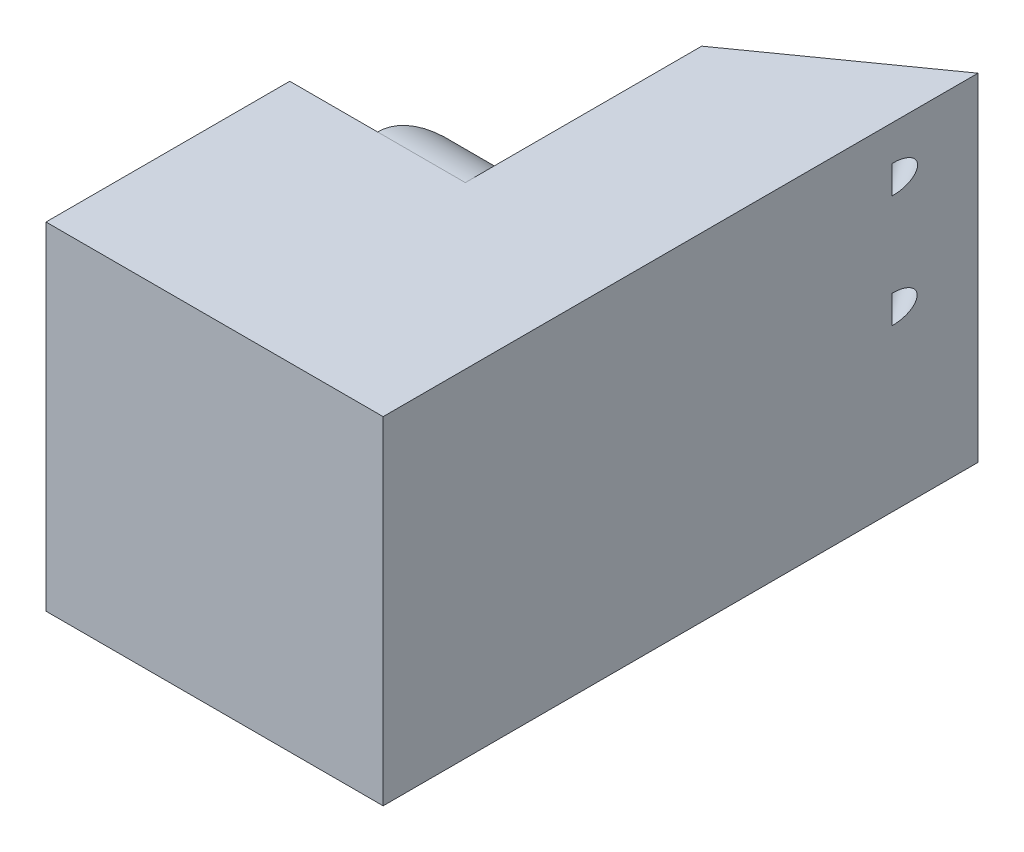
SolidWorks part; units mm, degrees
ref_plane "Front" through (0, 0, 0) normal (0, 0, 1) x (1, 0, 0)
ref_plane "Top" through (0, 0, 0) normal (0, 1, 0) x (1, 0, 0)
ref_plane "Right" through (0, 0, 0) normal (1, 0, 0) x (0, 0, -1)
sketch "Sketch1" plane through (0, 0, 0) normal (0, 1, 0) x (1, 0, 0)
  line L0 (48.006, 34.0858) -> (0, 0)
  line L1 (0, 0) -> (48.006, 0)
  line L2 (0, 0) -> (0, 34.0858)
  line L3 (0, 34.0858) -> (48.006, 34.0858)
  line L4 (48.006, 0) -> (48.006, 34.0858)
  dimension "D1" = 48.006
extrude "Boss-Extrude1" add sketch "Sketch1" along normal blind 48 contours L1 L4 L0 region at (32.004, 0, -11.3619)
sketch "Sketch2" plane through (0, 0, 0) normal (0, 0, 1) x (1, 0, 0)
  line L1 (0, 0) -> (48.006, 0)
  line L2 (0, 0) -> (0, 48)
  line L3 (0, 48) -> (48.006, 48)
  line L4 (48.006, 0) -> (48.006, 48)
extrude "Boss-Extrude2" add sketch "Sketch2" along normal blind 50.62
ref_plane "Plane1" through (0, 0, -34.09) normal (0, 0, 1) x (1, 0, 0)
sketch "Sketch3" plane through (0, 0, -34.09) normal (0, 0, 1) x (1, 0, 0)
  line L1 (0, 0) -> (25, 0)
  line L2 (0, 0) -> (0, 50.2391)
  line L3 (0, 50.2391) -> (25, 50.2391)
  line L4 (25, 0) -> (25, 50.2391)
  dimension "D1" = 25
extrude "Cut-Extrude1" cut sketch "Sketch3" along normal blind 40
ref_plane "Plane2" through (0, 0, 0) normal (-0.5789, 0, -0.8154) x (-0.8154, 0, 0.5789)
sketch "Sketch4" plane through (0, 0, 0) normal (-0.5789, 0, -0.8154) x (-0.8154, 0, 0.5789)
  line L0 (-58.8763, 48) -> (-58.8763, 0) construction
  line L2 (-58.8763, 48) -> (-30.6609, 48) construction
  circle A0 centre (-51.8973, 40.9808) radius 2
  circle A1 centre (-43.8763, 33) radius 11.315
  circle A2 centre (-35.8955, 41.0209) radius 2
  circle A3 centre (-35.8554, 25.0192) radius 2
  circle A4 centre (-51.8571, 24.9791) radius 2
  point P17 (-43.8763, 33)
  dimension "D1" = 15
  dimension "D2" = 15
  dimension "D3" = 4
extrude "Cut-Extrude2" cut sketch "Sketch4" against normal blind 10 contours A4 | A0 | A2 | A3
sketch "Sketch5" plane through (0, 0, 5.91) normal (0, 0, -1) x (-1, 0, 0)
  line L0 (-25, 48) -> (0, 48) construction
  line L1 (0, 0) -> (-12.5, 0)
  line L2 (0, 0) -> (0, 48)
  line L3 (0, 48) -> (-12.5, 48)
  line L4 (-12.5, 0) -> (-12.5, 48)
extrude "Cut-Extrude3" cut sketch "Sketch5" against normal blind 10
fillet "Fillet1" radius 10 3 edges at (18.75, 48, 5.91) (18.75, 0, 5.91) (12.5, 24, 5.91)
